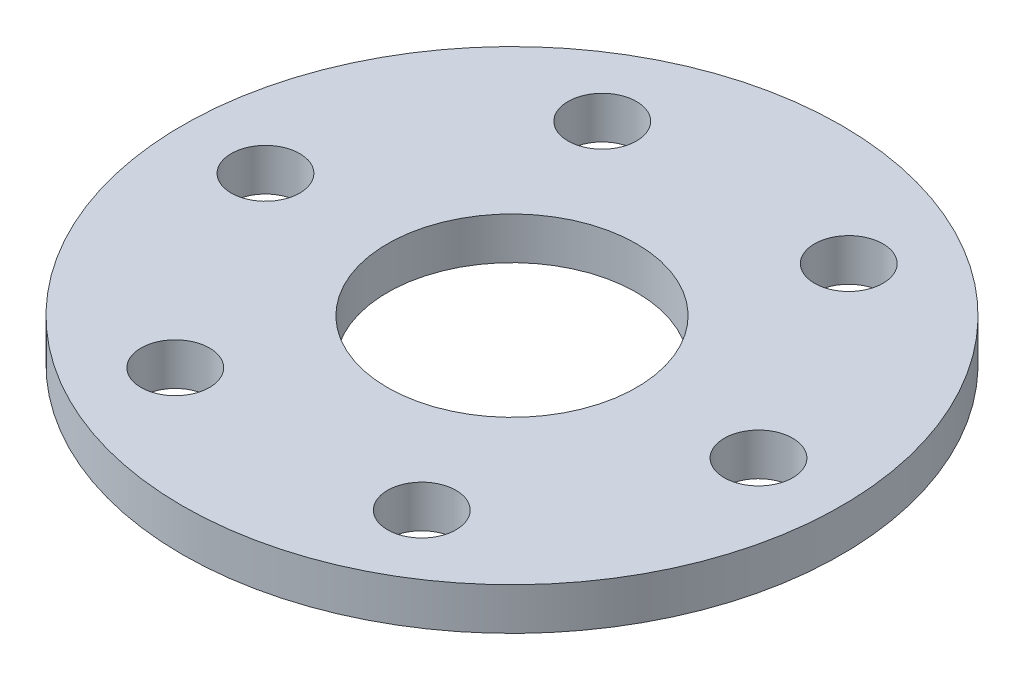
SolidWorks part; units mm, degrees
material "6063-O"
ref_plane "Front Plane" through (0, 0, 0) normal (0, 0, 1) x (1, 0, 0)
ref_plane "Top Plane" through (0, 0, 0) normal (0, 1, 0) x (1, 0, 0)
ref_plane "Right Plane" through (0, 0, 0) normal (1, 0, 0) x (0, 0, -1)
sketch "Sketch1" plane through (0, 0, 0) normal (0, 1, 0) x (1, 0, 0)
  circle A0 centre (0, 0) radius 31.75
  dimension "D1" = 63.5
extrude "Boss-Extrude1" add sketch "Sketch1" along normal blind 4.064
sketch "Sketch2" plane through (0, 4.064, 0) normal (0, 1, 0) x (1, 0, 0)
  line L0 (0, 0) -> (-23.75, 0) construction
  circle A0 centre (0, 0) radius 23.75 construction
  circle A1 centre (-23.75, 0) radius 2.6
  circle A2 centre (-11.875, 20.5681) radius 2.6
  circle A3 centre (11.875, 20.5681) radius 2.6
  circle A4 centre (23.75, 0) radius 2.6
  circle A5 centre (11.875, -20.5681) radius 2.6
  circle A6 centre (-11.875, -20.5681) radius 2.6
  point P17 (0, 0)
  dimension "D1" = 47.5
  dimension "D2" = 5.2
  dimension "D3" = 6
hole_wizard "M6 Clearance Hole1" positions "Sketch3" profile "Sketch4" hole size "M6" standard "ANSI Metric" end condition through all
sketch "Sketch3" plane through (0, 4.064, 0) normal (0, 1, 0) x (1, 0, 0)
  point P0 (-23.75, 0)
  point P3 (-11.875, 20.5681)
  point P6 (11.875, 20.5681)
  point P9 (23.75, 0)
  point P12 (11.875, -20.5681)
  point P15 (-11.875, -20.5681)
sketch "Sketch4" plane through (-23.75, 4.064, 0) normal (1, 0, 0) x (0, 0, 1)
  line L0 (0, 0) -> (0, 4.064)
  line L1 (0, 4.064) -> (3.3, 4.064)
  line L2 (3.3, 4.064) -> (3.3, 0)
  line L5 (3.3, 0) -> (0, 0)
  line L11 (0, -6.35) -> (0, 107.95) construction
  dimension "Thru Hole Dia." = 6.6
  dimension "Thru Hole Depth" = 4.064
sketch "Sketch5" plane through (0, 4.064, 0) normal (0, 1, 0) x (1, 0, 0)
  circle A0 centre (0, 0) radius 12
  dimension "D1" = 24
extrude "Cut-Extrude1" cut sketch "Sketch5" against normal through all
